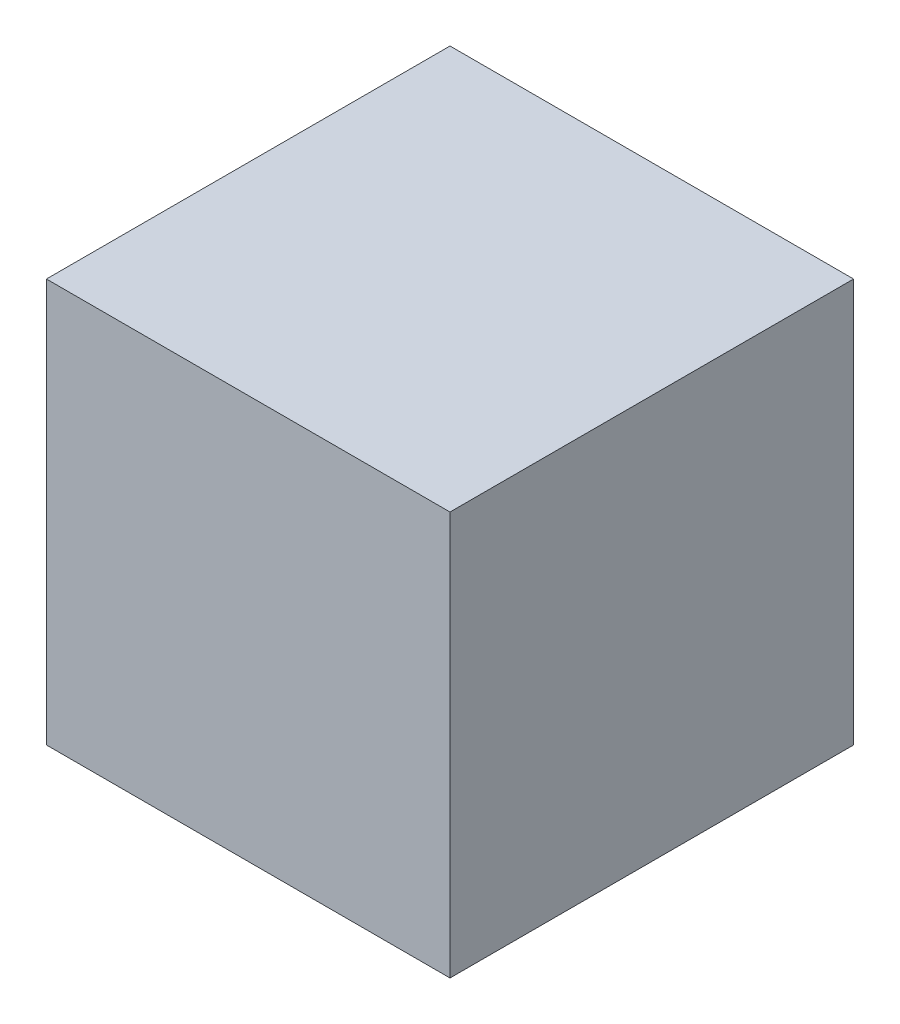
SolidWorks part; units mm, degrees
material "Nickel"
ref_plane "Front Plane" through (0, 0, 0) normal (0, 0, 1) x (1, 0, 0)
ref_plane "Top Plane" through (0, 0, 0) normal (0, 1, 0) x (1, 0, 0)
ref_plane "Right Plane" through (0, 0, 0) normal (1, 0, 0) x (0, 0, -1)
sketch "Sketch1" plane through (0, 0, 0) normal (0, 1, 0) x (1, 0, 0)
  line L1 (-1.5875, 1.5875) -> (1.5875, 1.5875)
  line L2 (-1.5875, 1.5875) -> (-1.5875, -1.5875)
  line L3 (-1.5875, -1.5875) -> (1.5875, -1.5875)
  line L4 (1.5875, 1.5875) -> (1.5875, -1.5875)
  line L5 (-1.5875, 1.5875) -> (1.5875, -1.5875) construction
  line L6 (-1.5875, -1.5875) -> (1.5875, 1.5875) construction
  point P0 (0, 0)
  dimension "D1" = 3.175
  dimension "D2" = 3.175
extrude "Boss-Extrude1" add sketch "Sketch1" along normal blind 3.175
